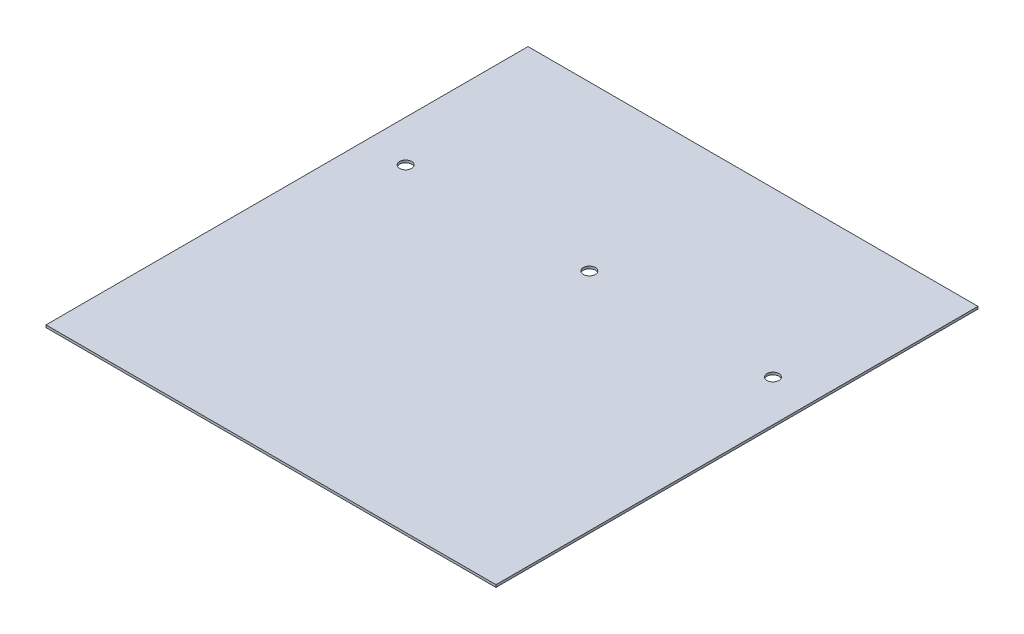
SolidWorks part; units mm, degrees
ref_plane "Front Plane" through (0, 0, 0) normal (0, 0, 1) x (1, 0, 0)
ref_plane "Top Plane" through (0, 0, 0) normal (0, 1, 0) x (1, 0, 0)
ref_plane "Right Plane" through (0, 0, 0) normal (1, 0, 0) x (0, 0, -1)
sketch "Sketch1" plane through (0, 0, 0) normal (0, 1, 0) x (1, 0, 0)
  line L0 (93.345, -199.9996) -> (93.345, -67.9196) construction
  line L1 (0, 0) -> (186.69, 0)
  line L2 (0, 0) -> (0, -199.9996)
  line L3 (0, -199.9996) -> (186.69, -199.9996)
  line L4 (186.69, 0) -> (186.69, -199.9996)
  line L5 (93.345, -67.9196) -> (186.69, -67.9196) construction
  line L6 (93.345, -67.9196) -> (0, -67.9196) construction
  circle A0 centre (93.345, -67.9196) radius 2.5
  circle A1 centre (17.145, -67.9196) radius 2.5
  circle A2 centre (93.345, -67.9196) radius 2.5
  circle A3 centre (169.545, -67.9196) radius 2.5
  dimension "D4" = 5
  dimension "D1" = 199.9996
  dimension "D2" = 186.69
  dimension "D3" = 132.08
  dimension "D5" = 2
  dimension "D6" = 2
extrude "Boss-Extrude1" add sketch "Sketch1" against normal blind 1 contours L4 L1 L2 L3 A3 A1 A0 region at (93.345, 0, 100.0505)
ref_plane "Plane1" through (93.345, 0, 0) normal (-1, 0, 0) x (0, 0, 1)
ref_plane "Plane2" through (0, 0, 99.9998) normal (0, 0, -1) x (-1, 0, 0)
ref_plane "Plane3" through (0, 0, 67.9196) normal (0, 0, 1) x (1, 0, 0)
